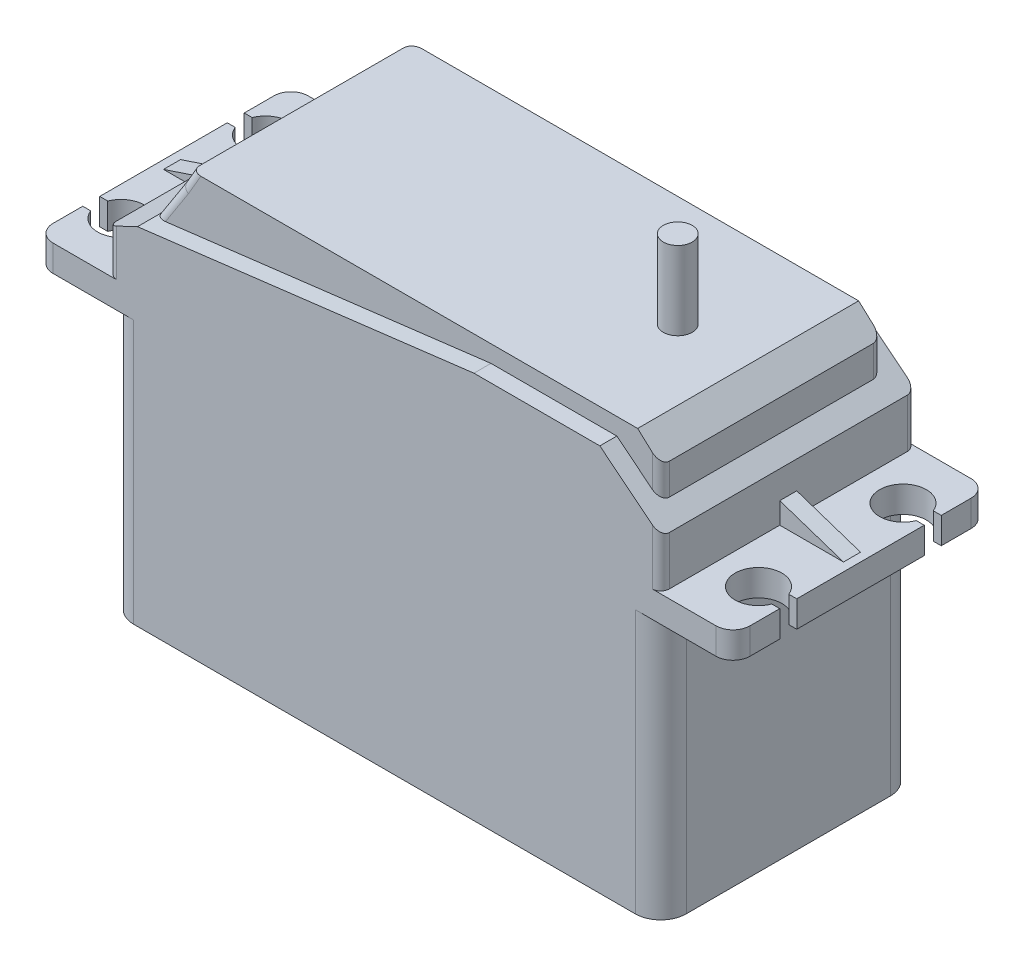
SolidWorks part; units mm, degrees
ref_plane "Front Plane" through (0, 0, 0) normal (0, 0, 1) x (1, 0, 0)
ref_plane "Top Plane" through (0, 0, 0) normal (0, 1, 0) x (1, 0, 0)
ref_plane "Right Plane" through (0, 0, 0) normal (1, 0, 0) x (0, 0, -1)
sketch "Sketch1" plane through (0, 0, 0) normal (0, 1, 0) x (1, 0, 0)
  line L1 (32.5, 0) -> (32.5, -15)
  line L2 (32.5, 0) -> (32.5, 15)
  line L4 (-32.5, 0) -> (-32.5, 15)
  line L5 (-32.5, 0) -> (-32.5, -15)
  line L6 (-32.5, 15) -> (32.5, 15)
  line L7 (-32.5, -15) -> (32.5, -15)
extrude "Boss-Extrude1" add sketch "Sketch1" along normal blind 31
sketch "Sketch2" plane through (0, 31, 0) normal (0, 1, 0) x (1, 0, 0)
  line L0 (0, 0) -> (41, 0)
  line L1 (41, 0) -> (41, -15)
  line L2 (41, 0) -> (41, 15)
  line L3 (0, 0) -> (0, 3.8779)
  line L4 (-41, 0) -> (-41, -15)
  line L5 (-41, 0) -> (-41, 15)
  line L6 (-41, 15) -> (41, 15)
  line L7 (41, -15) -> (-41, -15)
  line M2 (32.5, -15) -> (32.5, 15)
  line M4 (-32.5, 15) -> (-32.5, -15)
extrude "Boss-Extrude2" add sketch "Sketch2" along normal blind 3.1 contours L7 L6 L5 L4 M4 | L7 L1 L0 M2 | L6 L0 L2 M2 region at (36.75, 31, -7.5) region at (36.75, 31, 7.5) region at (31.7841, 31, 7.5) region at (-36.75, 31, 0)
fillet "Fillet2" radius 2 4 edges at (-41, 32.55, 15) (-41, 32.55, -15) (41, 32.55, -15) (41, 32.55, 15)
sketch "Sketch3" plane through (0, 34.1, 0) normal (0, 1, 0) x (1, 0, 0)
  line L0 (-41, 0) -> (-41, 8.5)
  line L1 (-41, -13) -> (-41, 13) construction
  line L2 (0, 15) -> (-37.5, 15)
  line L3 (39, 15) -> (-39, 15) construction
  line L4 (-37.5, 15) -> (-37.5, 8.5)
  line L5 (-37.5, 8.5) -> (-41, 8.5)
  line L6 (-41, 0) -> (-36.494, 0)
  line L7 (-37.5, -8.5) -> (-41, -8.5)
  line L8 (-37.5, -15) -> (-37.5, -8.5)
  line L9 (0, 15) -> (0, 8.5)
  circle A0 centre (-37.5, 8.5) radius 2.75
  circle A1 centre (-37.5, -8.5) radius 2.75
  circle A2 centre (37.5, 8.5) radius 2.75
  circle A3 centre (37.5, -8.5) radius 2.75
extrude "Cut-Extrude1" cut sketch "Sketch3" against normal blind 3.1 contours L4 A0 L5 | L5 A0 L4 | A1 L7 L8 | A1 L8 L7 | A2 | A3 region at (-37.111, 34.1, -8.111) region at (-38.6671, 34.1, -9.6671) region at (-38.6671, 34.1, 9.6671) region at (-37.111, 34.1, 8.111) region at (37.5, 34.1, -8.5) region at (37.5, 34.1, 8.5)
sketch "Sketch4" plane through (0, 34.1, 0) normal (0, 1, 0) x (1, 0, 0)
  line L0 (-41, 0) -> (-38.0561, 0)
  line L2 (-41, -13) -> (-41, 13) construction
  line L3 (0, 15) -> (0, 11.6555)
  line L4 (-40.25, -8) -> (-40.2042, -8)
  line L5 (-40.25, -9) -> (-40.2042, -9)
  line L6 (-40.25, -7.5) -> (-41, -7.5)
  line L7 (-40.25, -9.5) -> (-41, -9.5)
  line L8 (-40.25, -9.5) -> (-40.0617, -9.5)
  line L9 (-40.25, -7.5) -> (-40.0617, -7.5)
  line L10 (-41, -7.5) -> (-41, -9.5)
  line L11 (39, 15) -> (-39, 15) construction
  line L12 (-41, 7.5) -> (-41, 9.5)
  line L13 (-40.25, 7.5) -> (-40.0617, 7.5)
  line L14 (-40.25, 9.5) -> (-40.0617, 9.5)
  line L15 (-40.25, 9.5) -> (-41, 9.5)
  line L16 (-40.25, 7.5) -> (-41, 7.5)
  line L17 (-40.25, 9) -> (-40.2042, 9)
  line L18 (-40.25, 8) -> (-40.2042, 8)
  line L19 (40.25, -7.5) -> (40.0617, -7.5)
  line L20 (40.25, -7.5) -> (41, -7.5)
  line L21 (41, -7.5) -> (41, -9.5)
  line L22 (40.25, -9.5) -> (40.0617, -9.5)
  line L23 (40.25, -9.5) -> (41, -9.5)
  line L24 (40.25, -9) -> (40.2042, -9)
  line L25 (40.25, -8) -> (40.2042, -8)
  line L26 (40.25, 8) -> (40.2042, 8)
  line L27 (40.25, 9) -> (40.2042, 9)
  line L28 (40.25, 7.5) -> (41, 7.5)
  line L29 (40.25, 9.5) -> (41, 9.5)
  line L30 (40.25, 9.5) -> (40.0617, 9.5)
  line L31 (40.25, 7.5) -> (40.0617, 7.5)
  line L32 (41, 7.5) -> (41, 9.5)
  circle A0 centre (-37.5, -8.5) radius 2.75 construction
  arc A1 (-40.0617, -7.5) -> (-40.0617, -9.5) centre (-37.5, -8.5) ccw
  arc A2 (-40.0617, 7.5) -> (-40.0617, 9.5) centre (-37.5, 8.5) cw
  arc A3 (40.0617, -7.5) -> (40.0617, -9.5) centre (37.5, -8.5) cw
  arc A4 (40.0617, 7.5) -> (40.0617, 9.5) centre (37.5, 8.5) ccw
  point P37 (37.5, -8.5)
extrude "Cut-Extrude3" cut sketch "Sketch4" against normal blind 3.1 contours L16 L13 L6 L14 L15 L9 | L9 L6 L7 L8 L13 | L22 L23 L4 L20 L19 L10 | L31 L28 L4 L29 L30 L7 region at (-40.5921, 34.1, 8.5) region at (-40.5921, 34.1, -8.5) region at (40.5921, 34.1, 8.5) region at (40.5921, 34.1, -8.5)
sketch "Sketch5" plane through (0, 34.1, 0) normal (0, 1, 0) x (1, 0, 0)
  line L0 (0, 15) -> (-32.5, 15)
  line L1 (39, 15) -> (-39, 15) construction
  line L2 (-32.5, 15) -> (-32.5, -15)
  line L3 (-32.5, -15) -> (32.5, -15)
  line L4 (-39, -15) -> (39, -15) construction
  line L5 (32.5, -15) -> (32.5, 15)
  line L6 (32.5, 15) -> (0, 15)
extrude "Boss-Extrude3" add sketch "Sketch5" along normal blind 13.5
sketch "Sketch6" plane through (0, 47.6, 0) normal (0, 1, 0) x (1, 0, 0)
  line L0 (32.5, 15) -> (19.5, 15)
  line L1 (32.5, 15) -> (-32.5, 15) construction
  line L2 (19.5, 15) -> (19.5, 0)
  circle A0 centre (19.5, 0) radius 1.7
  circle A1 centre (19.5, 0) radius 5
sketch "Sketch7" plane through (0, 0, 15) normal (0, 0, 1) x (1, 0, 0)
  line L0 (-32.5, 34.1) -> (-32.5, 39.1)
  line L1 (-32.5, 47.6) -> (-32.5, 34.1) construction
  line L3 (-32.5, 47.6) -> (32.5, 47.6) construction
  line L4 (-24.6364, 47.6) -> (-32.5, 47.6)
  line L5 (-32.5, 47.6) -> (-32.5, 39.1)
  line L6 (-32.5, 39.1) -> (-29.0581, 40.7374)
  line L7 (-29.0581, 40.7374) -> (-24.6364, 47.6)
  line M11 (32.5, 47.6) -> (-32.5, 47.6)
  line M12 (-32.5, 47.6) -> (-32.5, 34.1)
extrude "Cut-Extrude5" cut sketch "Sketch7" against normal blind 43.2 contours L6 L7 M11 M12 region at (-29.653, 44.3164, 15)
sketch "Sketch8" plane through (0, 47.6, 0) normal (0, 1, 0) x (1, 0, 0)
  line L2 (-22.6364, -13) -> (30.5, -13)
  line L3 (32.5, -15) -> (32.5, 15) construction
  line L4 (30.5, 0) -> (27.1201, 0)
  line L5 (-25.7194, 15) -> (-25.7194, -15)
  line L6 (-22.6364, 13) -> (30.5, 13)
  line L7 (32.5, 13) -> (32.5, -13)
  line L9 (-24.6364, 15) -> (-22.6364, 15)
  line L10 (-24.6364, 15) -> (32.5, 15)
  line L12 (-24.6364, -15) -> (32.5, -15)
  line L13 (32.5, 15) -> (32.5, -15)
  line L14 (-22.6364, 13) -> (-22.6364, -13)
  line L15 (3.9318, 13) -> (3.9318, 6.4095)
  line L16 (30.5, 13) -> (30.5, -13)
  line L17 (-24.6364, 15) -> (-25.7194, 15)
  line L18 (-29.0581, 15) -> (-24.6364, 15) construction
  line L19 (-29.0581, -15) -> (-24.6364, -15) construction
  line L20 (-25.7194, -15) -> (-24.6364, -15)
  line M14 (-24.6364, 15) -> (-24.6364, -15)
  line M15 (-24.6364, -15) -> (32.5, -15)
  line M16 (32.5, -15) -> (32.5, 15)
  line M17 (32.5, 15) -> (-24.6364, 15)
extrude "Cut-Extrude7" cut sketch "Sketch8" against normal blind 2 contours L6 L16 L2 L14 M17 M14 M15 M16 | L5 L20 L17 M14 region at (-25.1779, 47.6, 0) region at (-23.6364, 47.6, -14.3547)
sketch "Sketch9" plane through (0, 0, 15) normal (0, 0, 1) x (1, 0, 0)
  line L0 (-25.7194, 45.6) -> (-25.9251, 45.6)
  line L1 (-29.0581, 40.7374) -> (-25.7194, 45.9192) construction
  line L2 (-25.9251, 45.6) -> (-25.7194, 45.9192)
  line L3 (-25.7194, 45.9192) -> (-25.7194, 45.6)
extrude "Cut-Extrude8" cut sketch "Sketch9" against normal blind 44
sketch "Sketch10" plane through (0, 0, 15) normal (0, 0, 1) x (1, 0, 0)
  line L0 (-29.0581, 40.7374) -> (10.5234, 45.6)
  line L1 (-25.9251, 45.6) -> (32.5, 45.6) construction
  line L2 (10.5234, 45.6) -> (-25.9251, 45.6)
  line L3 (-25.9251, 45.6) -> (-29.0581, 40.7374)
extrude "Cut-Extrude10" cut sketch "Sketch10" against normal blind 2
ref_plane "Plane2" through (0, 0, 0) normal (0, 0, 1) x (1, 0, 0)
mirror "Mirror2" about plane through (0, 0, 0) normal (0, 0, 1) of "Cut-Extrude10", "Cut-Extrude7"
sketch "Sketch11" plane through (0, 0, 0) normal (0, 0, 1) x (1, 0, 0)
  line L0 (-40, 34.1) -> (-32.5, 36.6)
  line L1 (-39, 34.1) -> (-41, 34.1) construction
  line L2 (-32.5, 39.1) -> (-32.5, 34.1) construction
  line L3 (-40, 34.1) -> (-32.5, 34.1)
  line L4 (-32.5, 34.1) -> (-32.5, 36.6)
  line L5 (0, 0) -> (0, 15.5296)
  line L6 (32.5, 34.1) -> (32.5, 36.6)
  line L7 (40, 34.1) -> (32.5, 34.1)
  line L8 (40, 34.1) -> (32.5, 36.6)
extrude "Boss-Extrude5" add sketch "Sketch11" along normal blind 1 and the other way blind 1 contours L0 L4 L3 | L8 L6 L7
sketch "Sketch13" plane through (0, 0, 15) normal (0, 0, 1) x (1, 0, 0)
  line L0 (25.3344, 45.6) -> (32.5, 39.85)
  line L1 (10.5234, 45.6) -> (30.5, 45.6) construction
  line L2 (32.5, 45.6) -> (32.5, 34.1) construction
  line L3 (32.5, 39.85) -> (32.5, 45.6)
  line L4 (10.5234, 45.6) -> (32.5, 45.6) construction
  line L5 (32.5, 45.6) -> (25.3344, 45.6)
extrude "Cut-Extrude11" cut sketch "Sketch13" against normal blind 2
sketch "Sketch14" plane through (0, 0, 13) normal (0, 0, 1) x (1, 0, 0)
  line L0 (27.7825, 47.6) -> (32.5, 43.2897)
  line L1 (-22.6364, 47.6) -> (30.5, 47.6) construction
  line L2 (32.5, 39.85) -> (32.5, 45.6) construction
  line L3 (32.5, 43.2897) -> (32.5, 47.6)
  line L4 (32.5, 47.6) -> (27.7825, 47.6)
extrude "Cut-Extrude12" cut sketch "Sketch14" against normal blind 40
mirror "Mirror16" about plane through (0, 0, 0) normal (0, 0, 1) of "Cut-Extrude11"
sketch "Sketch16" plane through (0, 0, 13) normal (0, 0, 1) x (1, 0, 0)
  line L1 (30.5, 43.2897) -> (30.5, 41.4549)
  line L2 (25.3344, 45.6) -> (32.5, 39.85) construction
  line L3 (30.5, 41.4549) -> (32.5, 39.85)
  line L4 (32.5, 39.85) -> (32.5, 43.2897)
  line L5 (30.5, 43.2897) -> (30.5, 45.1171)
  line L6 (27.7825, 47.6) -> (32.5, 43.2897) construction
  line L7 (30.5, 45.1171) -> (32.5, 43.2897)
extrude "Cut-Extrude14" cut sketch "Sketch16" against normal blind 40
sketch "Sketch17" plane through (0, 0, 13) normal (0, 0, 1) x (1, 0, 0)
  line L0 (-25.9251, 45.6) -> (-24.7605, 47.6)
  line L1 (-22.6364, 47.6) -> (-24.7605, 47.6)
  line L2 (-22.6364, 47.6) -> (-22.6364, 45.6)
  line L3 (-22.6364, 45.6) -> (-25.9251, 45.6)
extrude "Boss-Extrude6" add sketch "Sketch17" against normal up to surface (26 mm away) up to face at (2.7094, 44.9899, -13)
fillet "Fillet3" radius 1 10 edges at (-27.4916, 43.1687, -13) (-25.3428, 46.6, -13) (-25.3428, 46.6, 13) (-27.4916, 43.1687, 13) (30.5, 43.286, -13) (30.5, 43.286, 13) (32.5, 36.975, -15) (32.5, 36.975, 15) (-32.5, 36.6, -15) (-32.5, 36.6, 15)
extrude "Boss-Extrude7" add sketch "Sketch6" along normal up to surface (7.2 mm away) contours A0 region at (20.6681, 47.6, -1.1681)
fillet "Fillet4" radius 3 4 edges at (-32.5, 15.5, 15) (-32.5, 15.5, -15) (32.5, 15.5, -15) (32.5, 15.5, 15)
sketch "Sketch18" plane through (0, 54.8, 0) normal (0, 1, 0) x (1, 0, 0)
  circle A0 centre (19.5, 0) radius 1.7
sketch "Sketch19" plane through (0, 54.8, 0) normal (0, 1, 0) x (1, 0, 0)
extrude "Boss-Extrude11" add sketch "Sketch18" along normal blind 2
